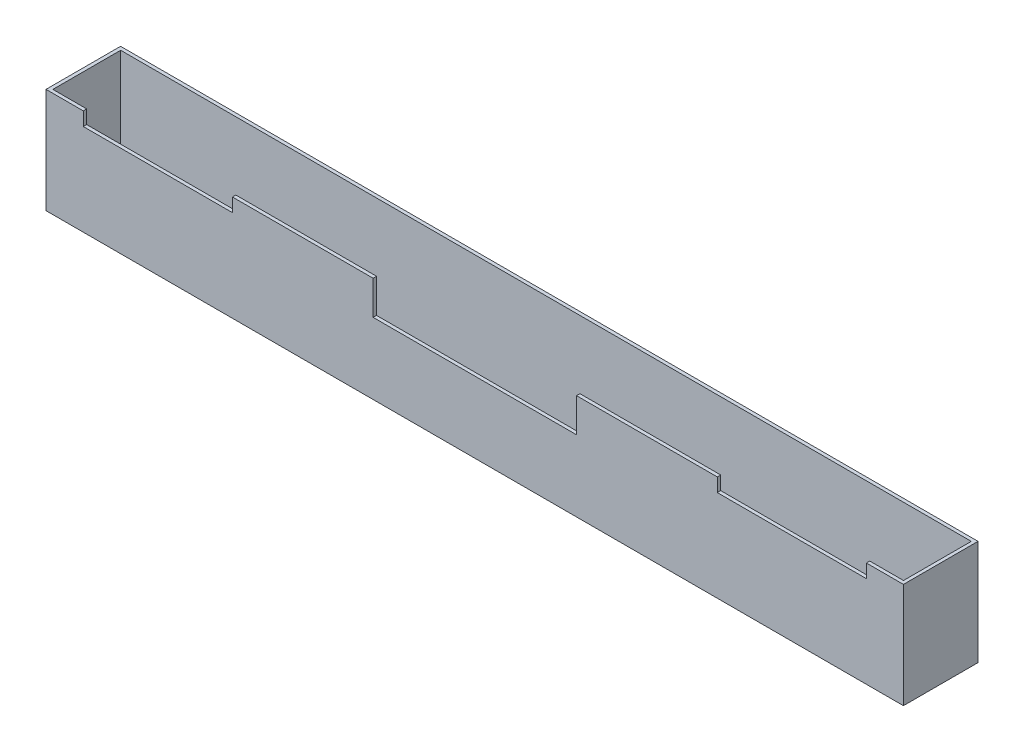
SolidWorks part; units mm, degrees
ref_plane "Front Plane" through (0, 0, 0) normal (0, 0, 1) x (1, 0, 0)
ref_plane "Top Plane" through (0, 0, 0) normal (0, 1, 0) x (1, 0, 0)
ref_plane "Right Plane" through (0, 0, 0) normal (1, 0, 0) x (0, 0, -1)
sketch "Sketch2" plane through (0, 0, 0) normal (0, 0, 1) x (1, 0, 0)
  line L0 (-401.701, 0) -> (-366.776, 0) construction
  line L1 (-401.701, 0) -> (-401.701, 98.425) construction
  line L2 (-401.701, 98.425) -> (401.447, 98.425) construction
  line L3 (401.447, 98.425) -> (401.447, 0) construction
  line L4 (-366.776, 0) -> (-227.076, 0) construction
  line L5 (-227.076, 0) -> (-100.076, 0) construction
  line L6 (-100.076, 0) -> (90.424, 0) construction
  line L7 (90.424, 0) -> (357.124, 0)
  line L9 (357.124, 0) -> (401.447, 0) construction
  line L10 (-401.701, 98.425) -> (-401.701, 0)
  line L11 (-401.701, 0) -> (-366.776, 0)
  line L15 (-227.076, 0) -> (-100.076, 0)
  line L23 (357.124, 0) -> (401.447, 0)
  line L24 (401.447, 0) -> (401.447, 98.425)
  line L25 (401.447, 98.425) -> (-401.701, 98.425)
  line L26 (-366.776, 0) -> (-227.076, 0)
  line L27 (-100.076, 0) -> (90.424, 0)
  dimension "D1" = 803.148
  dimension "D2" = 34.925
  dimension "D3" = 139.7
  dimension "D4" = 127
  dimension "D5" = 190.5
  dimension "D6" = 98.425
extrude "Boss-Extrude1" add sketch "Sketch2" along normal blind 69.85
sketch "Sketch3" plane through (0, 98.425, 0) normal (0, 1, 0) x (1, 0, 0)
  line L0 (0, 0) -> (-0.127, -69.85) construction
  line L1 (401.447, -69.85) -> (-401.701, -69.85) construction
  line L3 (-398.4625, -3.175) -> (398.3355, -3.175)
  line L4 (-398.4625, -3.175) -> (-398.4625, -66.675)
  line L5 (-398.4625, -66.675) -> (398.3355, -66.675)
  line L6 (398.3355, -3.175) -> (398.3355, -66.675)
  line L7 (-398.4625, -3.175) -> (398.3355, -66.675) construction
  line L8 (-398.4625, -66.675) -> (398.3355, -3.175) construction
  point P5 (-0.0635, -34.925)
  dimension "D1" = 796.798
  dimension "D2" = 63.5
extrude "Cut-Extrude1" cut sketch "Sketch3" against normal offset from surface (95.25 mm away) 3.175 up to face at (-0.127, 0, 34.925)
sketch "Sketch4" plane through (0, 0, 69.85) normal (0, 0, 1) x (1, 0, 0)
  line L0 (-401.701, 98.425) -> (-366.776, 98.425) construction
  line L1 (401.447, 98.425) -> (-401.701, 98.425) construction
  line L2 (-366.776, 98.425) -> (-227.076, 98.425) construction
  line L3 (-227.076, 98.425) -> (-95.25, 98.425) construction
  line L4 (-95.25, 98.425) -> (95.25, 98.425) construction
  line L5 (95.25, 98.425) -> (227.076, 98.425) construction
  line L6 (227.076, 98.425) -> (366.776, 98.425) construction
  line L7 (366.776, 98.425) -> (401.447, 98.425) construction
  line L8 (-366.776, 98.425) -> (-366.776, 85.725)
  line L9 (-366.776, 85.725) -> (-227.076, 85.725)
  line L10 (-227.076, 85.725) -> (-227.076, 189.9812)
  line L11 (-227.076, 189.9812) -> (-227.076, 207.9991)
  line L12 (-227.076, 207.9991) -> (-95.25, 207.9991)
  line L13 (-95.25, 207.9991) -> (-95.25, 98.425)
  line L14 (-95.25, 98.425) -> (-95.25, 66.675)
  line L15 (95.25, 98.425) -> (95.25, 66.675)
  line L16 (95.25, 66.675) -> (-95.25, 66.675)
  line L17 (95.25, 98.425) -> (95.25, 207.9991)
  line L18 (95.25, 207.9991) -> (227.076, 207.9991)
  line L19 (227.076, 207.9991) -> (227.076, 98.425)
  line L20 (227.076, 98.425) -> (227.076, 85.725)
  line L21 (227.076, 85.725) -> (366.776, 85.725)
  line L22 (366.776, 85.725) -> (366.776, 98.425)
  line L23 (366.776, 98.425) -> (366.776, 207.9991)
  line L24 (366.776, 207.9991) -> (366.776, 225.8181)
  line L25 (366.776, 225.8181) -> (-366.776, 225.8181)
  line L26 (-366.776, 225.8181) -> (-366.776, 207.9991)
  line L27 (-366.776, 207.9991) -> (-366.776, 98.425)
  dimension "D1" = 34.925
  dimension "D2" = 139.7
  dimension "D3" = 131.826
  dimension "D4" = 190.5
  dimension "D5" = 12.7
  dimension "D6" = 31.75
  dimension "D7" = 12.7
extrude "Cut-Extrude3" cut sketch "Sketch4" against normal up to surface (3.175 mm away) up to face at (-0.0635, 50.8, 66.675)
